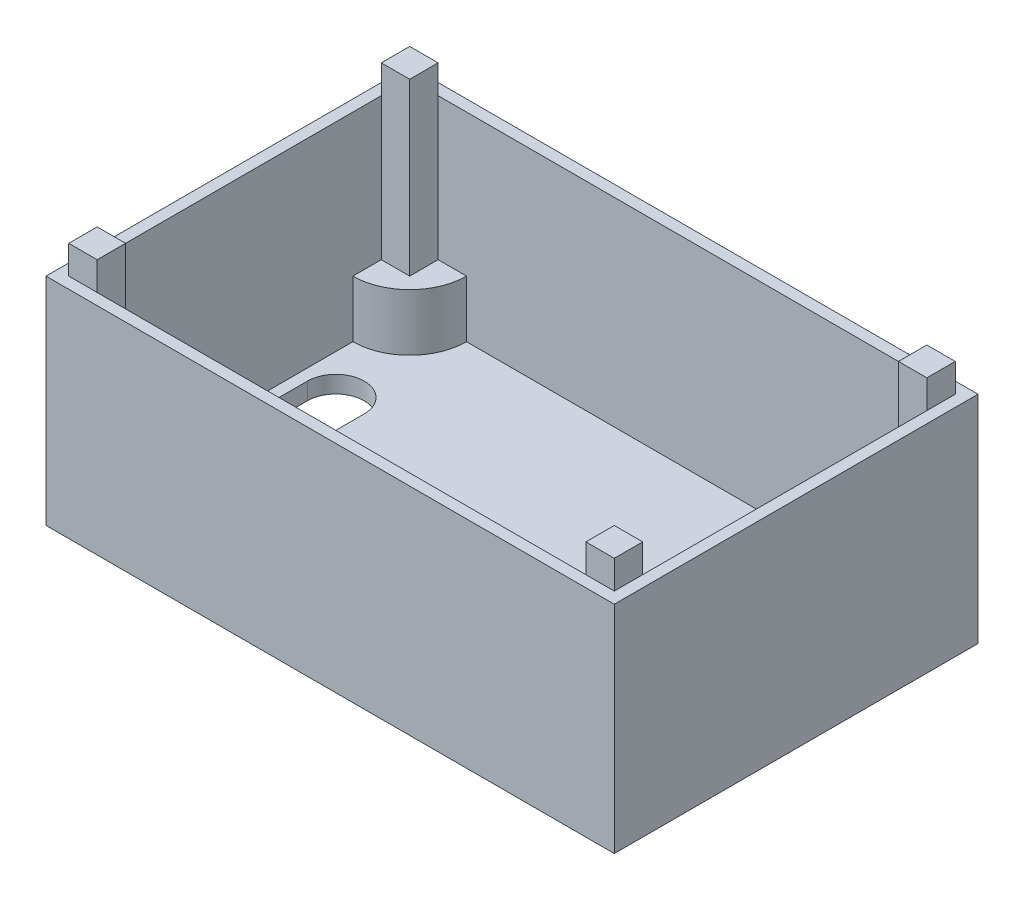
SolidWorks part; units mm, degrees
material "ABS"
ref_plane "Front Plane" through (0, 0, 0) normal (0, 0, 1) x (1, 0, 0)
ref_plane "Top Plane" through (0, 0, 0) normal (0, 1, 0) x (1, 0, 0)
ref_plane "Right Plane" through (0, 0, 0) normal (1, 0, 0) x (0, 0, -1)
sketch "Sketch1" plane through (0, 0, 0) normal (0, 1, 0) x (1, 0, 0)
  line L0 (-55, 0) -> (55, 0) construction
  line L1 (-50, 32) -> (50, 32)
  line L2 (-50, 32) -> (-50, -32)
  line L3 (-50, -32) -> (50, -32)
  line L4 (50, 32) -> (50, -32)
  line L5 (0, -55) -> (0, 55) construction
  dimension "D1" = 64
  dimension "D2" = 32
  dimension "D3" = 100
  dimension "D4" = 50
extrude "Boss-Extrude1" add sketch "Sketch1" along normal blind 3
sketch "Sketch2" plane through (0, 3, 0) normal (0, 1, 0) x (1, 0, 0)
  line L0 (50, 32) -> (-50, 32) construction
  line L1 (-48, -30) -> (48, -30)
  line L2 (-48, -30) -> (-48, 30)
  line L3 (-48, 30) -> (48, 30)
  line L4 (48, -30) -> (48, 30)
  line L5 (-48, -30) -> (48, 30) construction
  line L6 (-48, 30) -> (48, -30) construction
  line L7 (-50, 32) -> (-50, -32) construction
  line L9 (-50, 32) -> (50, 32)
  line L10 (-50, 32) -> (-50, -32)
  line L11 (-50, -32) -> (50, -32)
  line L12 (50, 32) -> (50, -32)
  point P0 (0, 0)
  dimension "D1" = 2
  dimension "D2" = 2
extrude "Boss-Extrude2" add sketch "Sketch2" along normal blind 35
sketch "Sketch12" plane through (0, 38, 0) normal (0, 1, 0) x (1, 0, 0)
  line L1 (-48, 30) -> (-43, 30)
  line L2 (-48, 30) -> (-48, 25)
  line L3 (-48, 25) -> (-43, 25)
  line L4 (-43, 30) -> (-43, 25)
  line L5 (0, 43.3275) -> (0, 0) construction
  line L6 (0, 0) -> (63.2414, 0) construction
  line L7 (43, 30) -> (43, 25)
  line L8 (48, 25) -> (43, 25)
  line L9 (48, 30) -> (48, 25)
  line L10 (48, 30) -> (43, 30)
  line L11 (48, -30) -> (48, -25)
  line L12 (48, -25) -> (43, -25)
  line L13 (48, -30) -> (43, -30)
  line L14 (43, -30) -> (43, -25)
  line L15 (-43, -30) -> (-43, -25)
  line L16 (-48, -25) -> (-43, -25)
  line L17 (-48, -30) -> (-48, -25)
  line L18 (-48, -30) -> (-43, -30)
  dimension "D1" = 5
  dimension "D2" = 5
extrude "Boss-Extrude9" add sketch "Sketch12" along normal blind 5 and the other way blind 37
sketch "Sketch14" plane through (0, 3, 0) normal (0, 1, 0) x (1, 0, 0)
  line L0 (-41, -10) -> (-41, 10) construction
  line L1 (-46, -10) -> (-46, 10)
  line L2 (-36, -10) -> (-36, 10)
  line L3 (-23.65, 0) -> (23.65, 0) construction
  line L4 (-48, 25) -> (-48, -25) construction
  arc A0 (-46, -10) -> (-36, -10) centre (-41, -10) ccw
  arc A1 (-36, 10) -> (-46, 10) centre (-41, 10) ccw
  point P2 (-41, 0)
  dimension "D3" = 5
  dimension "D1" = 0
  dimension "D2" = 2
  dimension "D4" = 20
extrude "Cut-Extrude6" cut sketch "Sketch14" against normal through all
sketch "Sketch17" plane through (0, 3, 0) normal (0, 1, 0) x (1, 0, 0)
  line L0 (0, 39.8656) -> (0, -43.9459) construction
  line L1 (-48, 30) -> (-38, 30)
  line L2 (-48, 30) -> (-48, 20)
  line L3 (-48, 20) -> (-38, 20)
  line L4 (-38, 30) -> (-38, 20)
  line L5 (-58.0064, 0) -> (59.7708, 0) construction
  line L6 (-23.65, 0) -> (23.65, 0) construction
  line L7 (48, 20) -> (38, 20)
  line L8 (48, 30) -> (48, 20)
  line L9 (48, 30) -> (38, 30)
  line L10 (38, 30) -> (38, 20)
  line L11 (48, -20) -> (38, -20)
  line L12 (48, -30) -> (38, -30)
  line L13 (38, -30) -> (38, -20)
  line L14 (-48, -30) -> (-48, -20)
  line L15 (-48, -30) -> (-38, -30)
  line L16 (-38, -30) -> (-38, -20)
  line L17 (-48, -20) -> (-38, -20)
  line M15 (48, -25) -> (48, 25)
  line M18 (43, 30) -> (-43, 30)
  line M21 (-48, 25) -> (-48, -25)
  line M24 (-43, -30) -> (43, -30)
  line M35 (-48, -25) -> (-43, -25)
  line M36 (-43, -25) -> (-43, -30)
  line M37 (43, -30) -> (43, -25)
  line M38 (43, -25) -> (48, -25)
  line M39 (48, 25) -> (43, 25)
  line M40 (43, 25) -> (43, 30)
  line M41 (-43, 30) -> (-43, 25)
  line M42 (-43, 25) -> (-48, 25)
  dimension "D1" = 10
  dimension "D2" = 10
extrude "Boss-Extrude11" add sketch "Sketch17" along normal blind 10 contours L4 L3 M18 M41 M42 M21 | L10 L7 M18 M15 M39 M40 | L13 L11 M24 M37 M38 M15 | L17 L16 M21 M35 M36 M24 region at (-42.1667, 3, -24.1667) region at (42.1667, 3, -24.1667) region at (-42.1667, 3, 24.1667) region at (42.1667, 3, 24.1667)
sketch "Sketch19" plane through (0, 0, 0) normal (0, -1, 0) x (1, 0, 0)
  line L0 (0, 39.645) -> (0, -39.8656) construction
  line L1 (-48, 30) -> (-43, 30)
  line L2 (-48, 30) -> (-48, 25)
  line L3 (-48, 25) -> (-43, 25)
  line L4 (-43, 30) -> (-43, 25)
  line L5 (-64.5128, 0) -> (62.6381, 0) construction
  line L6 (-50, 32) -> (50, 32) construction
  line L7 (-50, -32) -> (-50, 32) construction
  line L8 (43, 30) -> (43, 25)
  line L9 (48, 25) -> (43, 25)
  line L10 (48, 30) -> (48, 25)
  line L11 (48, 30) -> (43, 30)
  line L12 (48, -30) -> (48, -25)
  line L13 (48, -25) -> (43, -25)
  line L14 (43, -30) -> (43, -25)
  line L15 (48, -30) -> (43, -30)
  line L16 (-43, -30) -> (-43, -25)
  line L17 (-48, -25) -> (-43, -25)
  line L18 (-48, -30) -> (-48, -25)
  line L19 (-48, -30) -> (-43, -30)
  dimension "D1" = 2
  dimension "D2" = 2
  dimension "D3" = 5
  dimension "D4" = 5
extrude "Cut-Extrude7" cut sketch "Sketch19" against normal blind 7
fillet "Fillet2" radius 10 4 edges at (-38, 8, 20) (38, 8, -20) (38, 8, 20) (-38, 8, -20)
